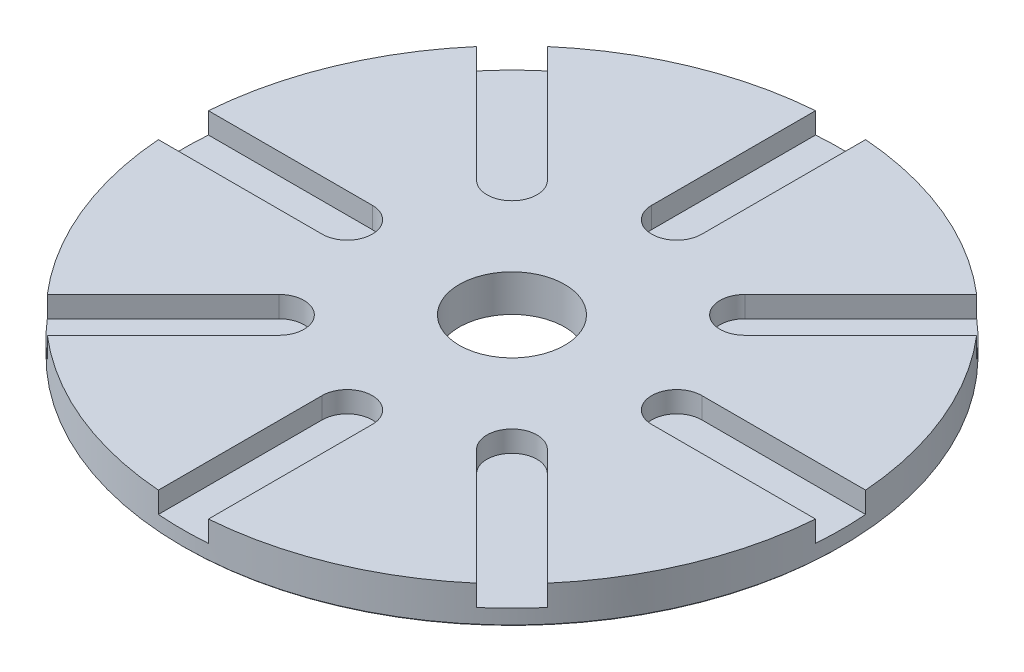
SolidWorks part; units mm, degrees
note: '?' marks a value the reader was unsure of.
ref_plane "前视基准面" through (0, 0, 0) normal (0, 0, 1) x (1, 0, 0)
ref_plane "上视基准面" through (0, 0, 0) normal (0, 1, 0) x (1, 0, 0)
ref_plane "右视基准面" through (0, 0, 0) normal (1, 0, 0) x (0, 0, -1)
sketch "草图1" plane through (0, 0, 0) normal (0, 1, 0) x (1, 0, 0)
  circle A0 centre (0, 0) radius 250
  dimension "D1" = 500
extrude "凸台-拉伸1" add sketch "草图1" along normal blind 50
sketch "草图8" plane through (0, 0, 0) normal (0, -1, 0) x (1, 0, 0)
  circle A0 centre (0, 0) radius 135
  dimension "D1" = 270
chamfer "倒角1" distance 1 angle 45 2 edges at (0, 0, 250) (0, 50, 250)
sketch "草图2" plane through (0, 50, 0) normal (0, 1, 0) x (1, 0, 0)
  line L0 (-288.8007, 0) -> (288.8007, 0) construction
  line L1 (125, 11) -> (250, 11)
  line L2 (125, -11) -> (250, -11)
  line L3 (250, 11) -> (250, -11)
  arc A0 (125, 11) -> (125, -11) centre (125, 0) ccw
  circle A2 centre (0, 0) radius 250 construction
  dimension "D1" = 11
  dimension "D2" = 125
  dimension "D3" = 125
extrude "切除-拉伸1" cut sketch "草图2" against normal blind 22
sketch "草图3" plane through (0, 28, 0) normal (0, 1, 0) x (1, 0, 0)
  line L0 (250, 19) -> (250, -19)
  line L1 (-16.6138, 0) -> (291.5513, 0) construction
  line L2 (125, 19) -> (250, 19)
  line L3 (125, -19) -> (250, -19)
  circle A0 centre (0, 0) radius 250 construction
  arc A3 (125, 19) -> (125, -19) centre (125, 0) ccw
  dimension "D1" = 38
extrude "切除-拉伸2" cut sketch "草图3" against normal blind 16
sketch "草图4" plane through (0, 50, 0) normal (0, 1, 0) x (1, 0, 0)
  line L0 (0, 0) -> (221.7597, 221.7597) construction
  line L1 (0, 0) -> (424.1081, 0) construction
  line L2 (168.9985, 184.5549) -> (184.5549, 168.9985)
  line L3 (96.1665, 80.6102) -> (184.5549, 168.9985)
  line L4 (80.6102, 96.1665) -> (168.9985, 184.5549)
  arc A0 (80.6102, 96.1665) -> (96.1665, 80.6102) centre (88.3883, 88.3883) ccw
  circle A1 centre (0, 0) radius 250 construction
  dimension "D2" = 11
  dimension "D1" = 45
  dimension "D3" = 125
  dimension "D4" = 125
extrude "切除-拉伸3" cut sketch "草图4" against normal blind 22
sketch "草图5" plane through (0, 28, 0) normal (0, 1, 0) x (1, 0, 0)
  line L0 (0, 0) -> (223.4089, 223.4089) construction
  line L1 (163.3417, 190.2117) -> (190.2117, 163.3417)
  line L2 (101.8234, 74.9533) -> (190.2117, 163.3417)
  line L3 (74.9533, 101.8234) -> (163.3417, 190.2117)
  arc A0 (74.9533, 101.8234) -> (101.8234, 74.9533) centre (88.3883, 88.3883) ccw
  arc A1 (-168.8273, -184.3837) -> (-249.7579, 11) centre (0, 0) ccw construction
  dimension "D1" = 19
extrude "切除-拉伸4" cut sketch "草图5" against normal blind 16
pattern_circular "阵列(圆周)1" count 4 over 360 about axis through (0, 0, 0) along (0, 1, 0) of "切除-拉伸1", "切除-拉伸2", "切除-拉伸3", "切除-拉伸4"
sketch "草图6" plane through (0, 50, 0) normal (0, 1, 0) x (1, 0, 0)
  circle A0 centre (0, 0) radius 60
  dimension "D1" = 120
extrude "切除-拉伸5" cut sketch "草图6" against normal blind 20
extrude "切除-拉伸12" [suppressed] cut sketch "草图8" against normal blind 6
hole_wizard "M12 六角凹头螺钉的柱形沉头孔1" [suppressed] positions "草图19" profile "草图18" counterbore size "M12" standard "ISO"
sketch "草图19" plane through (0, 50, 0) normal (0, 1, 0) x (-1, 0, 0)
  line L0 (0, 0) -> (-92.388, -38.2683) construction
  line L2 (0, 0) -> (-48.1243, 0) construction
  line L4 (-96.1665, -80.6102) -> (-183.6759, -168.1195) construction
  circle A0 centre (0, 0) radius 100 construction
  point P0 (-92.388, -38.2683)
  dimension "D1" = 200
  dimension "D2" = 22.5
  dimension "D3" = 22.5
sketch "草图18" plane through (92.388, 50, -38.2683) normal (1, 0, 0) x (0, 0, 1)
  line L0 (0, 0) -> (0, 50)
  line L1 (0, 50) -> (6.75, 50)
  line L3 (6.75, 50) -> (6.75, 14)
  line L4 (6.75, 14) -> (10, 14)
  line L5 (10, 14) -> (10, 0)
  line L7 (10, 0) -> (0, 0)
  line L11 (0, -6.35) -> (0, 107.95) construction
  dimension "通孔孔直径" = 13.5
  dimension "通孔孔深度" = 50
  dimension "柱形沉头孔直径" = 20
  dimension "柱形沉头孔深度" = 14
pattern_circular "阵列(圆周)2" [suppressed] count 8 over 360
hole_wizard "M12 螺纹孔1" [suppressed] positions "草图21" profile "草图20" tap size "M12" standard "GB"
sketch "草图21" [suppressed] plane through (0, 6, 0) normal (0, -1, 0) x (1, 0, 0)
  line L0 (0, 0) -> (0, 194.2317) construction
  line L2 (0, 0) -> (77.0348, 185.9785) construction
  circle A0 centre (0, 0) radius 120 construction
  point P0 (45.922, 110.8655)
  dimension "D1" = 240
  dimension "D2" = 22.5
sketch "草图20" plane through (45.922, 6, 110.8655) normal (1, 0, 0) x (0, 0, -1)
  line L0 (0, 0) -> (0, 35.8144)
  line L1 (0, 35.8144) -> (5.1, 32.75)
  line L2 (5.1, 32.75) -> (5.1, 0)
  line L5 (5.1, 0) -> (0, 0)
  line L10 (0, 35.8144) -> (-5.1, 32.75) construction
  line L11 (0, -6.35) -> (0, 107.95) construction
  dimension "螺纹孔钻头直径" = 10.2
  dimension "螺纹孔钻头深度" = 32.75
  dimension "导头角度" = 118
cosmetic thread "孔螺蚊线1" [suppressed] parameters "D1"=24, "D2"=12
pattern_circular "阵列(圆周)3" [suppressed] count 8 over 360
sketch "草图22" plane through (0, 30, 0) normal (0, 1, 0) x (1, 0, 0)
  circle A0 centre (0, 0) radius 40
  dimension "D1" = 80
extrude "切除-拉伸13" cut sketch "草图22" against normal through all
hole_wizard "M6 螺纹孔1" [suppressed] positions "草图24" profile "草图23" tap size "M6" standard "GB"
sketch "草图24" plane through (0, 30, 0) normal (0, 1, 0) x (-1, 0, 0)
  circle A0 centre (0, 0) radius 46 construction
  point P0 (0, 46)
  dimension "D1" = 92
sketch "草图23" plane through (0, 30, 46) normal (1, 0, 0) x (0, 0, 1)
  line L0 (0, 0) -> (0, 18.5022)
  line L1 (0, 18.5022) -> (2.5, 17)
  line L2 (2.5, 17) -> (2.5, 0)
  line L5 (2.5, 0) -> (0, 0)
  line L10 (0, 18.5022) -> (-2.5, 17) construction
  line L11 (0, -6.35) -> (0, 107.95) construction
  dimension "螺纹孔钻头直径" = 5
  dimension "螺纹孔钻头深度" = 17
  dimension "导头角度" = 118
cosmetic thread "孔螺蚊线2" [suppressed] parameters "D1"=12, "D2"=6
pattern_circular "阵列(圆周)4" [suppressed] count 6 over 360
ref_point "P0"
ref_axis "基准轴1" through (0, 50, 0) along (0, 0, 1)?
ref_axis "基准轴2" through (0, 50, 0) along (0, 1, 0)?
ref_plane "基准面1" [suppressed] through (0, 0, 0) normal (0.5, 0, 0.866) x (0, 1, 0)
ref_plane "基准面2" [suppressed] through (0, 0, 0) normal (0.866, 0, 0.5) x (0, 1, 0)
split "分割1" [suppressed] bodies to split 123
delete or keep bodies "实体-删除/保留 1" [suppressed] type keep bodies bodies 126
ref_plane "基准面3" through (0, 28, 0) normal (0, -1, 0) x (-1, 0, 0)
split "分割2" trim tools "基准面3" bodies to split 123 resulting bodies 128 129
delete or keep bodies "实体-删除/保留 2" type keep bodies bodies 128
